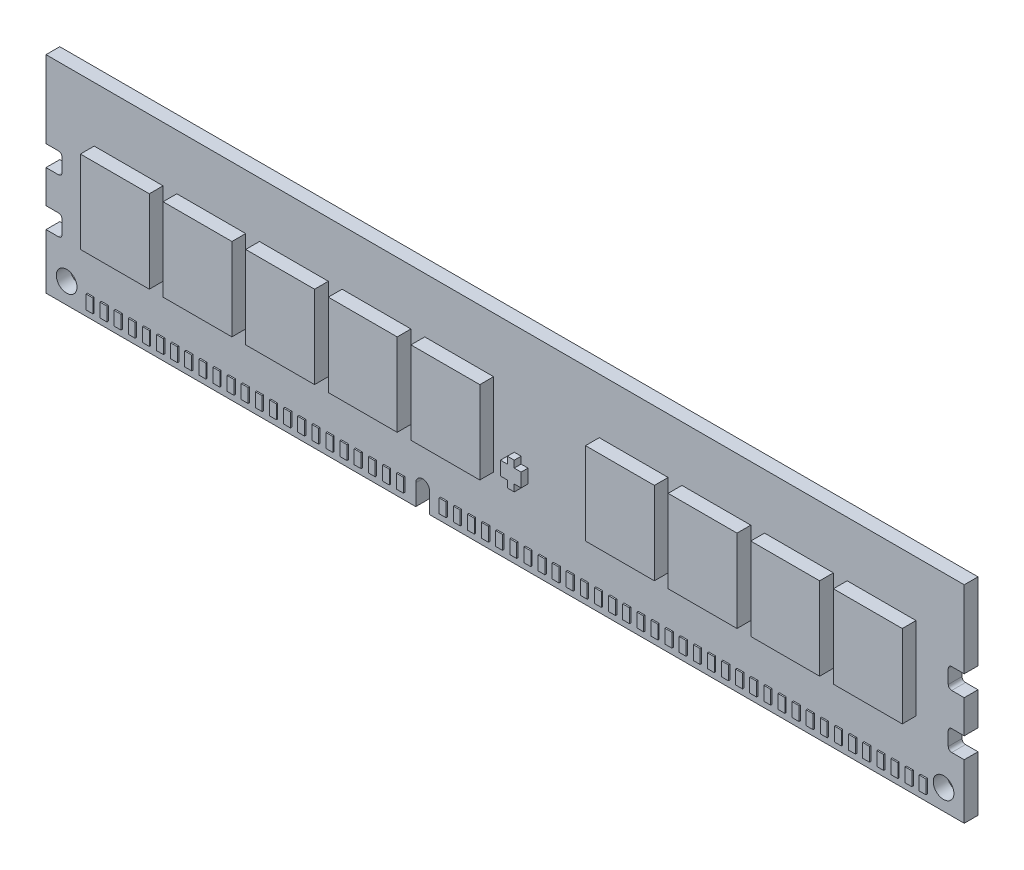
SolidWorks part; units mm, degrees
ref_plane "Front Plane" through (0, 0, 0) normal (0, 0, 1) x (1, 0, 0)
ref_plane "Top Plane" through (0, 0, 0) normal (0, 1, 0) x (1, 0, 0)
ref_plane "Right Plane" through (0, 0, 0) normal (1, 0, 0) x (0, 0, -1)
sketch "Sketch1" plane through (0, 0, 0) normal (0, 0, 1) x (1, 0, 0)
  line L1 (0, 0) -> (133.35, 0)
  line L2 (0, 0) -> (0, 30)
  line L3 (0, 30) -> (133.35, 30)
  line L4 (133.35, 0) -> (133.35, 30)
  dimension "D1" = 133.35
  dimension "D2" = 30
extrude "PCB" add sketch "Sketch1" along normal mid plane 2
sketch "Sketch2" plane through (0, 0, 1) normal (0, 0, 1) x (1, 0, 0)
  line L0 (0, 30) -> (0, 0) construction
  line L1 (0, 18.8) -> (2.3205, 18.8)
  line L2 (0, 18.8) -> (0, 15.8)
  line L3 (0, 15.8) -> (2.3205, 15.8)
  line L4 (2.3205, 18.8) -> (2.3205, 15.8)
  line L5 (0, 0) -> (133.35, 0) construction
  line L6 (0, 11) -> (2.3205, 11)
  line L7 (0, 11) -> (0, 8)
  line L8 (0, 8) -> (2.3205, 8)
  line L9 (2.3205, 11) -> (2.3205, 8)
  line L10 (66.675, 30) -> (66.675, 0) construction
  line L11 (133.35, 30) -> (0, 30) construction
  line L12 (131.0295, 11) -> (131.0295, 8)
  line L13 (133.35, 8) -> (131.0295, 8)
  line L14 (133.35, 11) -> (133.35, 8)
  line L15 (133.35, 11) -> (131.0295, 11)
  line L16 (131.0295, 18.8) -> (131.0295, 15.8)
  line L17 (133.35, 15.8) -> (131.0295, 15.8)
  line L18 (133.35, 18.8) -> (133.35, 15.8)
  line L19 (133.35, 18.8) -> (131.0295, 18.8)
  line L21 (53.7, 0) -> (55.7, 0)
  line L22 (53.7, 0) -> (53.7, 4)
  line L23 (53.7, 4) -> (55.7, 4)
  line L24 (55.7, 0) -> (55.7, 4)
  point P10 (1.1603, 8)
  point P29 (53.7, 2)
  dimension "D1" = 8
  dimension "D2" = 11
  dimension "D3" = 15.8
  dimension "D4" = 18.8
  dimension "D5" = 2
  dimension "D6" = 53.7
  dimension "D7" = 4
extrude "Cut-Extrude1" cut sketch "Sketch2" against normal blind 2
hole_wizard "Ø3.0mm Dowel Hole1" positions "Sketch9" profile "Sketch10" hole size "Ø3.0" standard "ANSI Metric" end condition through all
sketch "Sketch9" plane through (0, 0, 1) normal (0, 0, 1) x (1, 0, 0)
  line L0 (0, 8) -> (0, 0) construction
  line L1 (0, 0) -> (53.7, 0) construction
  line L2 (66.675, 30) -> (66.675, 0) construction
  line L3 (133.35, 30) -> (0, 30) construction
  line L4 (55.7, 0) -> (133.35, 0) construction
  point P0 (3, 3)
  point P19 (130.35, 3)
  dimension "D1" = 3
  dimension "D2" = 3
sketch "Sketch10" plane through (3, 3, 1) normal (1, 0, 0) x (0, -1, 0)
  line L0 (0, 0) -> (0, 2)
  line L1 (0, 2) -> (1.5, 2)
  line L2 (1.5, 2) -> (1.5, 0)
  line L5 (1.5, 0) -> (0, 0)
  line L11 (0, -6.35) -> (0, 107.95) construction
  dimension "Thru Hole Dia." = 3
  dimension "Thru Hole Depth" = 2
sketch "Sketch11" plane through (0, 0, 1) normal (0, 0, 1) x (1, 0, 0)
  line L0 (66.675, 30) -> (66.675, 0) construction
  line L1 (133.35, 30) -> (0, 30) construction
  line L2 (55.7, 0) -> (133.35, 0) construction
  line L3 (0, 30) -> (0, 18.8) construction
  line L4 (7, 22) -> (17, 22)
  line L5 (7, 22) -> (7, 10)
  line L6 (7, 10) -> (17, 10)
  line L7 (17, 22) -> (17, 10)
  line L20 (0, 0) -> (53.7, 0) construction
  dimension "D1" = 10
  dimension "D2" = 12
  dimension "D3" = 7
  dimension "D4" = 10
extrude "Boss-Extrude2" add sketch "Sketch11" along normal blind 2
pattern_linear "LPattern1" count 5 spacing 12 along (1, 0, 0) of "Boss-Extrude2"
sketch "Sketch12" plane through (0, 0, 1) normal (0, 0, 1) x (1, 0, 0)
  line L1 (116.35, 22) -> (126.35, 22)
  line L2 (116.35, 22) -> (116.35, 10)
  line L3 (116.35, 10) -> (126.35, 10)
  line L4 (126.35, 22) -> (126.35, 10)
  line L6 (133.35, 11) -> (133.35, 15.8) construction
  dimension "D1" = 10
  dimension "D2" = 7
extrude "Boss-Extrude3" add sketch "Sketch12" along normal blind 2
pattern_linear "LPattern2" count 4 spacing 12 along (-1, 0, 0) of "Boss-Extrude3"
mirror "Mirror1" about plane through (0, 0, 0) normal (0, 0, 1) of "LPattern2", "Boss-Extrude3", "LPattern1", "Boss-Extrude2"
sketch "Sketch13" plane through (0, 0, 1) normal (0, 0, 1) x (1, 0, 0)
  line L0 (65, 10) -> (65, 22) construction
  line L1 (67, 13) -> (70, 13)
  line L2 (67, 13) -> (67, 11)
  line L3 (67, 11) -> (70, 11)
  line L4 (70, 13) -> (70, 11)
  line L5 (68, 11) -> (69, 11)
  line L6 (68, 11) -> (68, 10)
  line L7 (68, 10) -> (69, 10)
  line L8 (69, 11) -> (69, 10)
  line L9 (68, 13) -> (69, 13)
  line L10 (68, 13) -> (68, 14)
  line L11 (68, 14) -> (69, 14)
  line L12 (69, 13) -> (69, 14)
  point P12 (69, 10.5)
  dimension "D1" = 1
  dimension "D2" = 2
  dimension "D3" = 1
  dimension "D4" = 1
  dimension "D5" = 3
  dimension "D6" = 1
  dimension "D7" = 2
extrude "Boss-Extrude4" add sketch "Sketch13" along normal blind 1 contours L4 L1 L2 L3 | L10 L9 L12 L11 | L6 L5 L8 L7 region at (68.5, 12, 1)
sketch "Sketch14" plane through (0, 0, 1) normal (0, 0, 1) x (1, 0, 0)
  line L0 (0, 0) -> (53.7, 0) construction
  line L1 (6, 3) -> (7, 3)
  line L2 (6, 3) -> (6, 1)
  line L3 (6, 1) -> (7, 1)
  line L4 (7, 3) -> (7, 1)
  line L5 (0, 8) -> (0, 0) construction
  dimension "D1" = 1
  dimension "D2" = 3
  dimension "D3" = 1
  dimension "D4" = 6
extrude "Boss-Extrude5" add sketch "Sketch14" along normal blind 0.2
pattern_linear "LPattern3" count 23 spacing 2.05 along (1, 0, 0) of "Boss-Extrude5"
sketch "Sketch15" plane through (0, 0, 1) normal (0, 0, 1) x (1, 0, 0)
  line L1 (57.3, 3) -> (58.3, 3)
  line L2 (57.3, 3) -> (57.3, 1)
  line L3 (57.3, 1) -> (58.3, 1)
  line L4 (58.3, 3) -> (58.3, 1)
  line L7 (55.7, 0) -> (55.7, 4) construction
  line L8 (53.7, 4) -> (53.7, 0) construction
  line L9 (52.1, 3) -> (52.1, 1) construction
  line L10 (52.1, 1) -> (52.1, 3) construction
  dimension "D1" = 1
  dimension "D2" = 1.6
  dimension "D3" = 1.6
extrude "Boss-Extrude6" add sketch "Sketch15" along normal blind 0.2
pattern_linear "LPattern4" count 35 spacing 2.05 along (1, 0, 0) of "Boss-Extrude6"
mirror "Mirror2" about plane through (0, 0, 0) normal (0, 0, 1) of "LPattern4", "Boss-Extrude6", "LPattern3"
fillet "Fillet1" radius 0.5 8 edges at (131.0295, 8, 0) (131.0295, 15.8, 0) (131.0295, 11, 0) (131.0295, 18.8, 0) (2.3205, 8, 0) (2.3205, 11, 0) (2.3205, 15.8, 0) (2.3205, 18.8, 0)
fillet "Fillet2" radius 1 2 edges at (53.7, 4, 0) (55.7, 4, 0)
